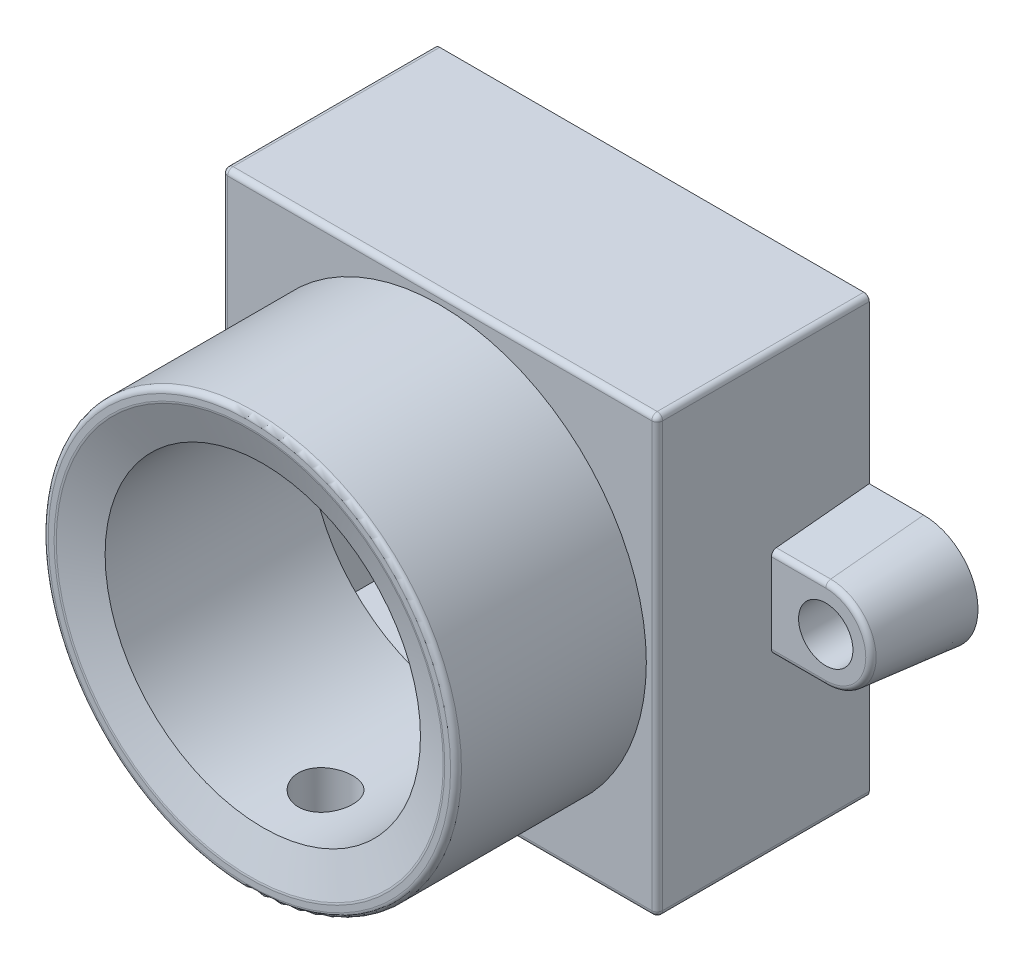
SolidWorks part; units mm, degrees
ref_plane "前视基准面" through (0, 0, 0) normal (0, 0, 1) x (1, 0, 0)
ref_plane "上视基准面" through (0, 0, 0) normal (0, 1, 0) x (1, 0, 0)
ref_plane "右视基准面" through (0, 0, 0) normal (1, 0, 0) x (0, 0, -1)
sketch "草图1" plane through (0, 0, 0) normal (0, 0, 1) x (1, 0, 0)
  line L1 (-8, -8) -> (8, -8)
  line L2 (-8, -8) -> (-8, 8)
  line L3 (-8, 8) -> (8, 8)
  line L4 (8, -8) -> (8, 8)
  line L5 (-8, -8) -> (8, 8) construction
  line L6 (-8, 8) -> (8, -8) construction
  point P0 (0, 0)
  point P5 (-0.8359, 0)
  dimension "D1" = 16
extrude "凸台-拉伸1" add sketch "草图1" along normal blind 7.8
sketch "草图2" plane through (0, 0, 7.8) normal (0, 0, 1) x (1, 0, 0)
  circle A0 centre (0, 0) radius 7.6
  point P2 (1.8483, 1.3818)
  dimension "D1" = 15.2
extrude "凸台-拉伸2" add sketch "草图2" along normal blind 7
sketch "草图3" plane through (0, 0, 0) normal (0, 0, -1) x (-1, 0, 0)
  line L0 (10, 0) -> (0, 0) construction
  line L1 (10, 2) -> (4, 2)
  line L2 (10, 2) -> (10, -2)
  line L3 (10, -2) -> (4, -2)
  line L4 (4, 2) -> (4, -2)
  circle A0 centre (10, 0) radius 2
  point P0 (0, 0)
  point P8 (13.1405, -6.3556)
  point P10 (0, 0)
  line M9 (8, -8) -> (8, 8)
  dimension "D1" = 4
  dimension "D2" = 10
  dimension "D3" = 6
extrude "凸台-拉伸3" add sketch "草图3" against normal blind 3.6 draft 5.5 contours L0 L4 L3 M9 | L2 A0 | L0 L1 L4 M9 | L2 L0 A0 | L0 L2 A0 | A0 L1 M9 | A0 L3 M9 region at (-9.1512, -0.8488, 0) region at (-9.1512, 0.8488, 0) region at (-10.8488, 0, 0) region at (-6, -1, 0) region at (-8.4467, 1.5533, 0) region at (-8.4467, -1.5533, 0) region at (-6, 1, 0)
sketch "草图4" plane through (0, 0, 3.6) normal (0, 0, 1) x (1, 0, 0)
  circle A0 centre (-10, 0) radius 1
  arc A1 (-10, 1.6534) -> (-10, -1.6534) centre (-10, 0) ccw construction
  point P2 (0, 0)
  dimension "D1" = 2
extrude "切除-拉伸1" cut sketch "草图4" against normal through all
fillet "圆角1" radius 0.2 3 edges at (-9, 1.6534, 3.6) (-11.6534, 0, 3.6) (-9, -1.6534, 3.6)
mirror "镜向1" about plane through (0, 0, 0) normal (1, 0, 0) of "圆角1", "切除-拉伸1", "凸台-拉伸3"
sketch "草图5" plane through (0, 0, 0) normal (0, 0, -1) x (-1, 0, 0)
  line L1 (7.1, -7.1) -> (-7.1, -7.1)
  line L2 (7.1, -7.1) -> (7.1, 7.1)
  line L3 (7.1, 7.1) -> (-7.1, 7.1)
  line L4 (-7.1, -7.1) -> (-7.1, 7.1)
  line L5 (7.1, -7.1) -> (-7.1, 7.1) construction
  line L6 (7.1, 7.1) -> (-7.1, -7.1) construction
  dimension "D1" = 14.2
extrude "切除-拉伸2" cut sketch "草图5" against normal blind 6.8
sketch "草图6" plane through (0, 0, 6.8) normal (0, 0, -1) x (-1, 0, 0)
  circle A0 centre (0, 0) radius 5.8
  point P0 (0, 0)
  dimension "D1" = 11.6
extrude "切除-拉伸3" cut sketch "草图6" against normal through all
chamfer "倒角1" distance 1.35 angle 20 1 edges at (-5.8, 0, 14.8) first distance on face at (-5.8, 0, 14.8)
fillet "圆角2" radius 0.2 2 edges at (7.6, 0, 14.8) (7.15, 0, 14.8)
sketch "草图7" plane through (0, 0, 0) normal (0, 1, 0) x (1, 0, 0)
  line L0 (0, 0) -> (0, -12) construction
  circle A0 centre (0, -12) radius 1
  point P2 (0, 0)
  point P5 (0, 0)
  point P6 (0, 0)
  dimension "D2" = 2
  dimension "D1" = 12
extrude "切除-拉伸4" cut sketch "草图7" against normal through all
fillet "圆角3" radius 0.2 8 edges at (-8, 0, 7.8) (0, 8, 7.8) (8, 0, 7.8) (0, -8, 7.8) (-8, 8, 3.9) (8, 8, 3.9) (8, -8, 3.9) (-8, -8, 3.9)
